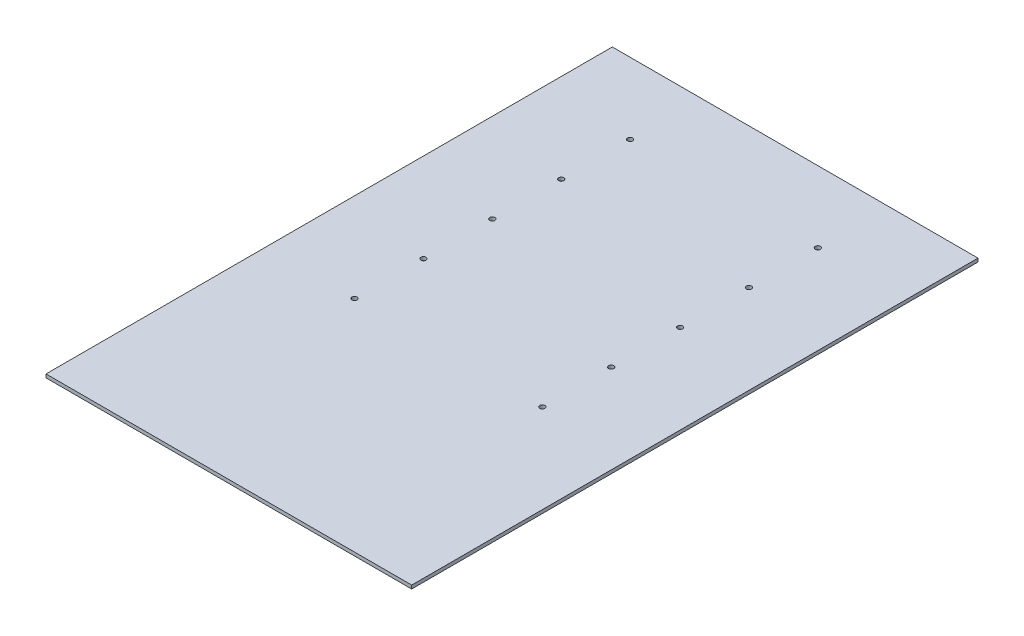
SolidWorks part; units mm, degrees
ref_plane "前视基准面" through (0, 0, 0) normal (0, 0, 1) x (1, 0, 0)
ref_plane "上视基准面" through (0, 0, 0) normal (0, 1, 0) x (1, 0, 0)
ref_plane "右视基准面" through (0, 0, 0) normal (1, 0, 0) x (0, 0, -1)
other "Configuration Table"
sketch "草图1" plane through (0, 0, 0) normal (0, 1, 0) x (1, 0, 0)
  line L1 (-159.28, 246.665) -> (159.28, 246.665)
  line L2 (-159.28, 246.665) -> (-159.28, -246.665)
  line L3 (-159.28, -246.665) -> (159.28, -246.665)
  line L4 (159.28, 246.665) -> (159.28, -246.665)
  line L5 (-159.28, 246.665) -> (159.28, -246.665) construction
  line L6 (-159.28, -246.665) -> (159.28, 246.665) construction
  circle A0 centre (81.78, 184.6607) radius 2.25 construction
  circle A1 centre (81.78, 184.6607) radius 2.25
  circle A2 centre (81.78, 124.6607) radius 2.25 construction
  circle A3 centre (81.78, 124.6607) radius 2.25
  circle A4 centre (81.78, 64.6607) radius 2.25 construction
  circle A5 centre (81.78, 64.6607) radius 2.25
  circle A6 centre (81.78, -55.3393) radius 2.25 construction
  circle A7 centre (81.78, -55.3393) radius 2.25
  circle A8 centre (81.78, 4.6607) radius 2.25 construction
  circle A9 centre (81.78, 4.6607) radius 2.25
  circle A10 centre (-81.78, -55.3393) radius 2.25 construction
  circle A11 centre (-81.78, -55.3393) radius 2.25
  circle A12 centre (-81.78, 4.6607) radius 2.25 construction
  circle A13 centre (-81.78, 4.6607) radius 2.25
  circle A14 centre (-81.78, 64.6607) radius 2.25 construction
  circle A15 centre (-81.78, 64.6607) radius 2.25
  circle A16 centre (-81.78, 124.6607) radius 2.25 construction
  circle A17 centre (-81.78, 124.6607) radius 2.25
  circle A18 centre (-81.78, 184.6607) radius 2.25 construction
  circle A19 centre (-81.78, 184.6607) radius 2.25
  point P0 (0, 0)
  dimension "D1" = 318.56
  dimension "D2" = 493.33
extrude "凸台-拉伸1" add sketch "草图1" along normal blind 3
